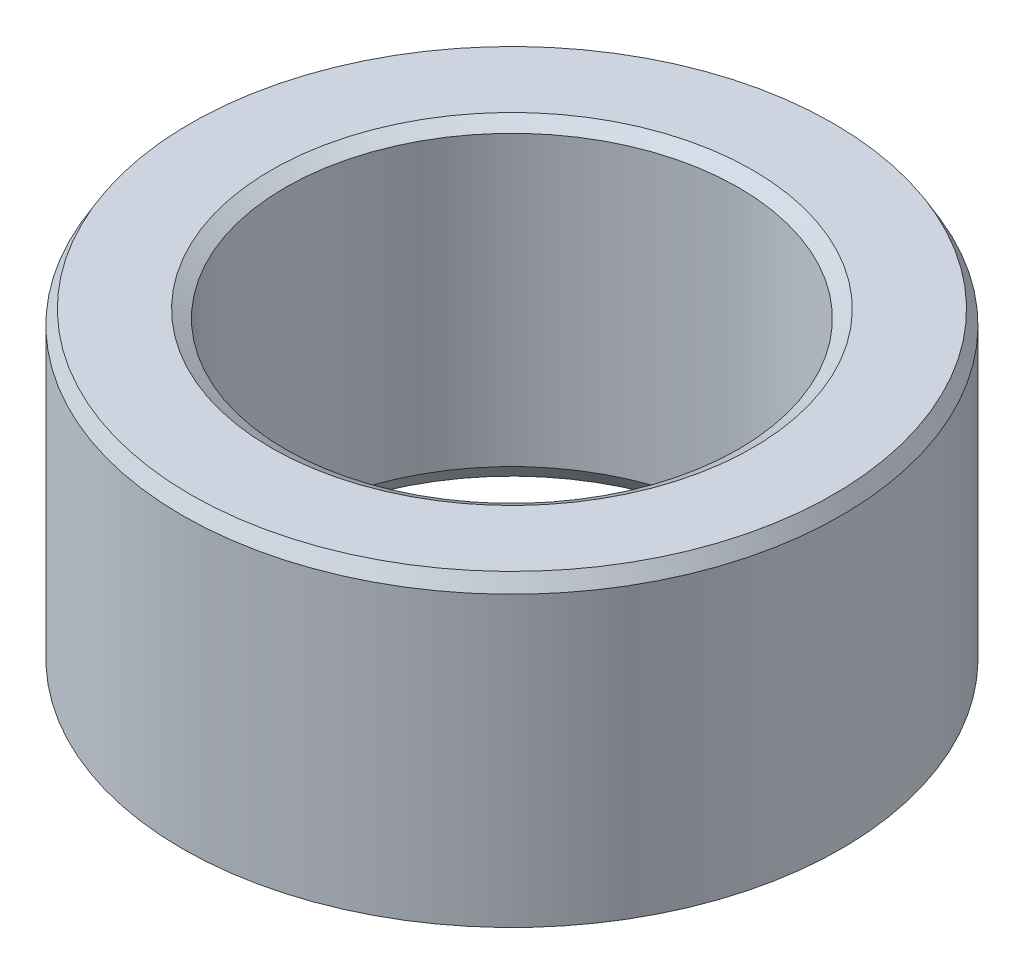
SolidWorks part; units mm, degrees
ref_plane "Front Plane" through (0, 0, 0) normal (0, 0, 1) x (1, 0, 0)
ref_plane "Top Plane" through (0, 0, 0) normal (0, 1, 0) x (1, 0, 0)
ref_plane "Right Plane" through (0, 0, 0) normal (1, 0, 0) x (0, 0, -1)
sketch "Sketch1" plane through (0, 0, 0) normal (0, 1, 0) x (1, 0, 0)
  circle A0 centre (0, 0) radius 35
  dimension "SLEEVE_OD" = 70
extrude "Boss-Extrude1" add sketch "Sketch1" along normal blind 33.0033
sketch "Sketch2" plane through (0, 0, 0) normal (0, 1, 0) x (1, 0, 0)
  circle A0 centre (0, 0) radius 24.0685
  dimension "BORE_D" = 48.137
extrude "Cut-Extrude1" cut sketch "Sketch2" along normal through all
chamfer "Chamfer1" distance 1.4919 angle 30 4 edges at (0, 33.0033, 24.0685) (0, 0, 24.0685) (0, 0, 35) (0, 33.0033, 35) first distance on face at (0, 33.0033, 24.0685) first distance on face at (0, 0, 24.0685) first distance on face at (0, 33.0033, 35)
